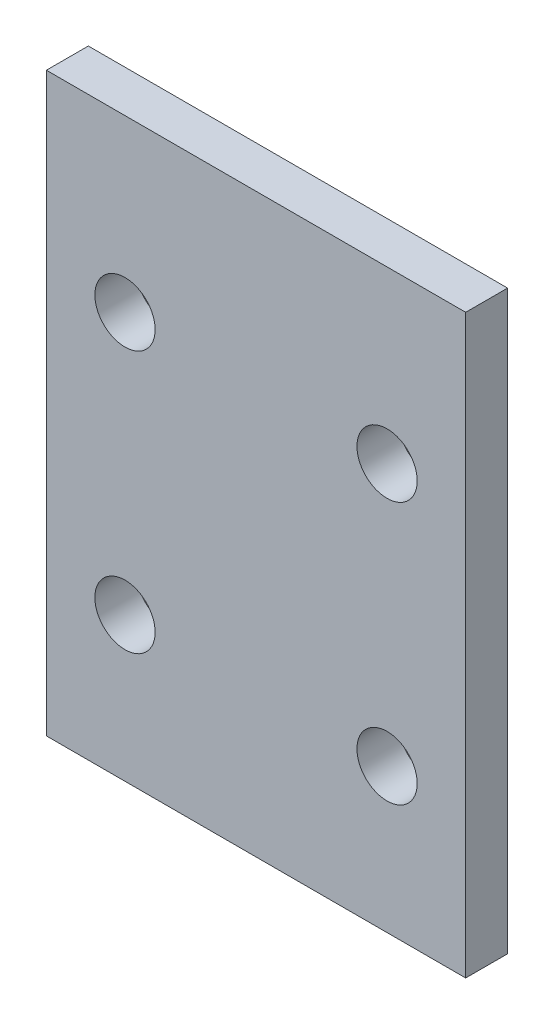
SolidWorks part; units mm, degrees
note: The reader was unsure of these and kept them because the rebuilt part matched: thickness of "Базовая кромка1", "Листовой металл1", "Листовой металл2".
material "Простая углеродистая сталь"
ref_plane "Спереди" through (0, 0, 0) normal (0, 0, 1) x (1, 0, 0)
ref_plane "Сверху" through (0, 0, 0) normal (0, 1, 0) x (1, 0, 0)
ref_plane "Справа" through (0, 0, 0) normal (1, 0, 0) x (0, 0, -1)
sketch "Эскиз1" plane through (0, 0, 0) normal (0, 0, 1) x (1, 0, 0)
  line L1 (0, 0) -> (160, 0)
  line L2 (0, 0) -> (0, -220)
  line L3 (0, -220) -> (160, -220)
  line L4 (160, 0) -> (160, -220)
  line L5 (80, -220) -> (80, 0) construction
  line L6 (0, -110) -> (160, -110) construction
  point P208 (80, -110)
  dimension "D1" = 160
  dimension "D2" = 220
base flange "Базовая кромка1" sketch "Эскиз1" thickness 16 reverse thickness direction no parameters "D1"=1
sketch "Эскиз2" plane through (0, 0, -16) normal (0, 0, -1) x (-1, 0, 0)
  line L0 (-80, 0) -> (-80, -220) construction
  line L2 (-160, 0) -> (0, 0) construction
  line L3 (0, -220) -> (-160, -220) construction
  circle A0 centre (-30, -165) radius 11.5
  circle A1 centre (-30, -65) radius 11.5
  circle A2 centre (-130, -165) radius 11.5
  circle A3 centre (-130, -65) radius 11.5
  dimension "D1" = 23
  dimension "D4" = 100
  dimension "D5" = 100
  dimension "D2" = 55
  dimension "D3" = 2
extrude "Вырез-Вытянуть1" cut sketch "Эскиз2" against normal blind 30 normal cut yes
sketch "Сгиб-Линии1" plane through (0, 0, 0) normal (0, 1, 0) x (1, 0, 0)
sketch "Граничная рамка1" plane through (0, 0, 0) normal (0, 1, 0) x (1, 0, 0)
sheet metal parameters "Листовой металл1" thickness 16 parameters "D1"=1, "D7"=4
flat pattern "Развертка1" [suppressed]
sketch "Сгиб-Линии2" plane through (0, 0, 0) normal (0, 1, 0) x (1, 0, 0)
sketch "Граничная рамка2" [suppressed] plane through (0, 0, 0) normal (0, 1, 0) x (1, 0, 0)
sheet metal parameters "Листовой металл2" thickness 16 parameters "D1"=1, "D7"=4
flat pattern "Развертка1"
sketch "Сгиб-Линии2" plane through (0, 0, 0) normal (0, 1, 0) x (1, 0, 0)
sketch3d "Граничная рамка2" [suppressed]
  line L0 (160, 0, 0) -> (160, -220, 0) construction
  line L1 (0, 0, 0) -> (0, -220, 0) construction
  line L2 (160, 0, 0) -> (0, 0, 0) construction
  line L3 (160, -220, 0) -> (0, -220, 0) construction
